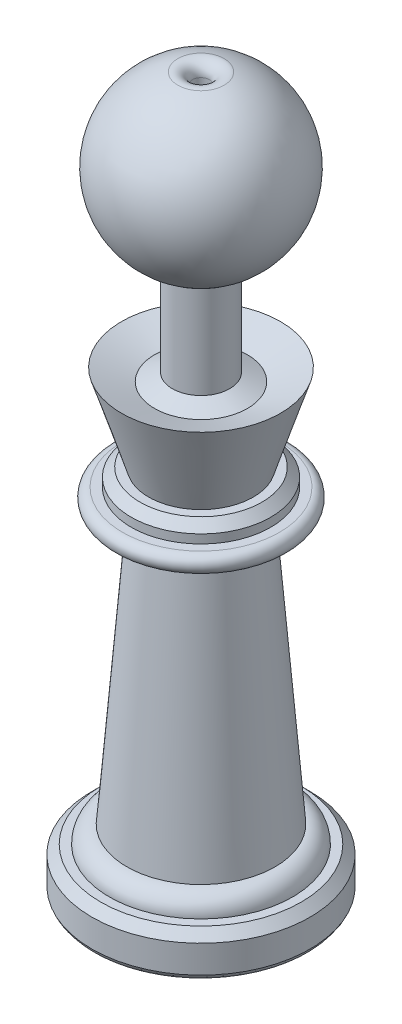
SolidWorks part; units mm, degrees
ref_plane "Front Plane" through (0, 0, 0) normal (0, 0, 1) x (1, 0, 0)
ref_plane "Top Plane" through (0, 0, 0) normal (0, 1, 0) x (1, 0, 0)
ref_plane "Right Plane" through (0, 0, 0) normal (1, 0, 0) x (0, 0, -1)
sketch "Sketch2" plane through (0, 0, 0) normal (0, 0, 1) x (1, 0, 0)
  line L0 (0, 0) -> (0, 41.275)
  line L1 (0, 0) -> (-9.525, 0)
  line L2 (-9.525, 0) -> (-9.525, 3.175)
  line L3 (-9.525, 3.175) -> (-8.001, 3.175)
  line L4 (-8.001, 3.175) -> (-8.001, 4.699)
  line L5 (-8.001, 4.699) -> (-6.477, 4.699)
  line L6 (-6.477, 4.699) -> (-4.572, 28.6766)
  line L7 (-4.572, 28.6766) -> (-6.858, 28.6766)
  line L8 (-7.62, 29.4386) -> (-7.62, 30.2006) construction
  line L9 (-6.858, 30.2006) -> (-6.096, 30.2006)
  line L10 (-6.096, 30.2006) -> (-6.096, 31.7246)
  line L11 (-6.096, 31.7246) -> (-4.572, 31.7246)
  line L12 (-4.572, 31.7246) -> (-6.9468, 39.2544)
  line L13 (-6.9468, 39.2544) -> (-4.064, 38.179)
  line L14 (-4.064, 38.179) -> (-0.3789, 39.8519)
  line L15 (-0.3789, 39.8519) -> (0, 40.0239) construction
  line L16 (-7.62, 28.6766) -> (-7.62, 29.4386) construction
  line L17 (-6.858, 28.6766) -> (-7.62, 28.6766) construction
  line L18 (-7.62, 30.2006) -> (-6.858, 30.2006) construction
  arc A0 (0, 41.275) -> (-0.3789, 39.8519) centre (0, 40.513) ccw
  arc A1 (-0.3789, 39.8519) -> (0, 39.751) centre (0, 40.513) ccw construction
  arc A2 (0, 39.751) -> (0, 41.275) centre (0, 40.513) ccw construction
  arc A3 (-6.858, 30.2006) -> (-6.858, 28.6766) centre (-6.858, 29.4386) ccw
  dimension "D14" = 1.524
  dimension "D1" = 41.275
  dimension "D2" = 9.525
  dimension "D3" = 3.175
  dimension "D4" = 1.524
  dimension "D5" = 1.524
  dimension "D6" = 1.524
  dimension "D7" = 1.524
  dimension "D8" = 28.6766
  dimension "D9" = 1.524
  dimension "D10" = 1.524
  dimension "D12" = 7.62
  dimension "D13" = 1.524
revolve "Revolve1" add sketch "Sketch2" angle 360 about L0
fillet "Fillet1" radius 1.524 1 edges at (0, 4.699, -8.001)
chamfer "Chamfer1" distance 0.762 angle 45 1 edges at (0, 3.175, -9.525)
chamfer "Chamfer2" distance 0.762 angle 45 1 edges at (0, 31.7246, -6.096)
sketch "Sketch3" plane through (0, 3.175, 0) normal (0, 1, 0) x (1, 0, 0)
  point P0 (0, 0)
sketch "Sketch4" plane through (0, 0, 0) normal (0, -1, 0) x (1, 0, 0)
  circle A0 centre (0, 0) radius 9.525 construction
  point P0 (0, 0)
  point P1 (9.525, 0)
ref_plane "Plane1" through (0, 0, 0) normal (0, 0, 1) x (1, 0, 0)
sketch "Sketch5" plane through (0, 0, 0) normal (0, 0, 1) x (1, 0, 0)
  line L0 (0, 0) -> (-10, 0)
  line L1 (-10, 0) -> (-5.37, -2.68)
  line L2 (-5.37, -2.68) -> (0, -2.68)
  line L3 (0, -2.68) -> (0, 0)
  line L4 (0, 37.661) -> (0, 73.2558) construction
  line L5 (0, 34.8252) -> (-2.5, 34.8252)
  line L6 (0, 34.8252) -> (0, 47.32)
  line L7 (0, 47.32) -> (-2.5, 47.32)
  line L8 (-2.5, 34.8252) -> (-2.5, 47.32)
  circle A0 centre (0, 54.3911) radius 7.5
  dimension "D7" = 15
  dimension "D1" = 10
  dimension "D2" = 5.37
  dimension "D3" = 2.68
  dimension "D4" = 2.5
  dimension "D5" = 2.5
  dimension "D6" = 50
revolve "Revolve2" add sketch "Sketch5" angle 360 about L4 region at (-3.9587, -1.2054, 0) region at (-0.9412, 47.148, 0) region at (-3.2015, 54.4505, 0)
sketch "Sketch6" plane through (0, -2.68, 0) normal (0, -1, 0) x (1, 0, 0)
  circle A0 centre (0, 0) radius 0.75
  dimension "D1" = 1.5
extrude "Cut-Extrude1" cut sketch "Sketch6" against normal blind 65
sketch "Sketch7" plane through (0, -2.68, 0) normal (0, -1, 0) x (1, 0, 0)
  circle A0 centre (0, 0) radius 5.1
  dimension "D1" = 10.2
extrude "Cut-Extrude2" cut sketch "Sketch7" against normal blind 4 contours A0
fillet "Fillet2" radius 1 3 edges at (0, 61.8535, -0.75) (0, 0, -10) (0, -2.68, -5.1)
